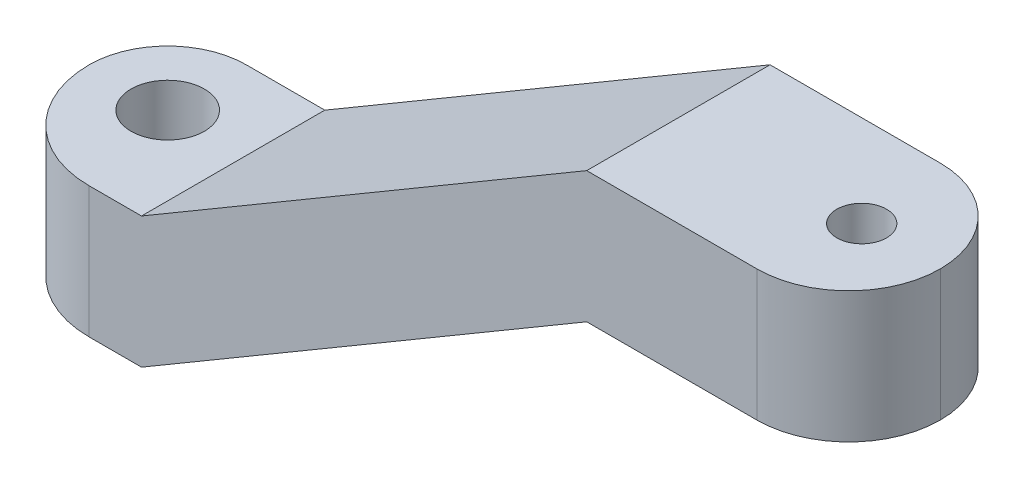
SolidWorks part; units mm, degrees
ref_plane "Plan de face" through (0, 0, 0) normal (0, 0, 1) x (1, 0, 0)
ref_plane "Plan de dessus" through (0, 0, 0) normal (0, 1, 0) x (1, 0, 0)
ref_plane "Plan de droite" through (0, 0, 0) normal (1, 0, 0) x (0, 0, -1)
sketch "Esquisse1" plane through (0, 0, 0) normal (0, 0, 1) x (1, 0, 0)
  line L0 (17, 15) -> (0, 5)
  line L1 (0, 0) -> (-6, 0)
  line L3 (0, 5) -> (-6, 5)
  line L4 (-6, 0) -> (-6, 5)
  line L5 (17, 15) -> (27, 15)
  line L7 (17, 10) -> (27, 10)
  line L8 (27, 15) -> (27, 10)
  line L9 (0, 0) -> (17, 10)
  dimension "D1" = 6
  dimension "D2" = 15
  dimension "D3" = 10
  dimension "D4" = 27
  dimension "D5" = 5
  dimension "D6" = 6
  dimension "D7" = 5
extrude "Boss.-Extru.1" add sketch "Esquisse1" along normal blind 7
sketch "Esquisse3" plane through (0, 5, 0) normal (0, 1, 0) x (1, 0, 0)
  line L0 (0, 0) -> (-6, 0) construction
  line L1 (-6, -7) -> (-6, 0) construction
  circle A0 centre (-3, -3) radius 1.4
  dimension "D3" = 2.8
  dimension "D1" = 3
  dimension "D2" = 3
extrude "Enlèv. mat.-Extru.1" cut sketch "Esquisse3" against normal blind 7
sketch "Esquisse4" plane through (0, 15, 0) normal (0, 1, 0) x (1, 0, 0)
  line L0 (27, 0) -> (17, 0) construction
  line L1 (27, -7) -> (27, 0) construction
  circle A0 centre (24, -3.5) radius 0.95
  dimension "D1" = 1.9
  dimension "D2" = 3.5
  dimension "D3" = 3
extrude "Enlèv. mat.-Extru.2" cut sketch "Esquisse4" against normal blind 7
fillet "Congé1" radius 3.5 2 edges at (27, 12.5, 7) (27, 12.5, 0)
fillet "Congé2" radius 4 1 edges at (-6, 2.5, 7)
fillet "Congé3" radius 3 1 edges at (-6, 2.5, 0)
